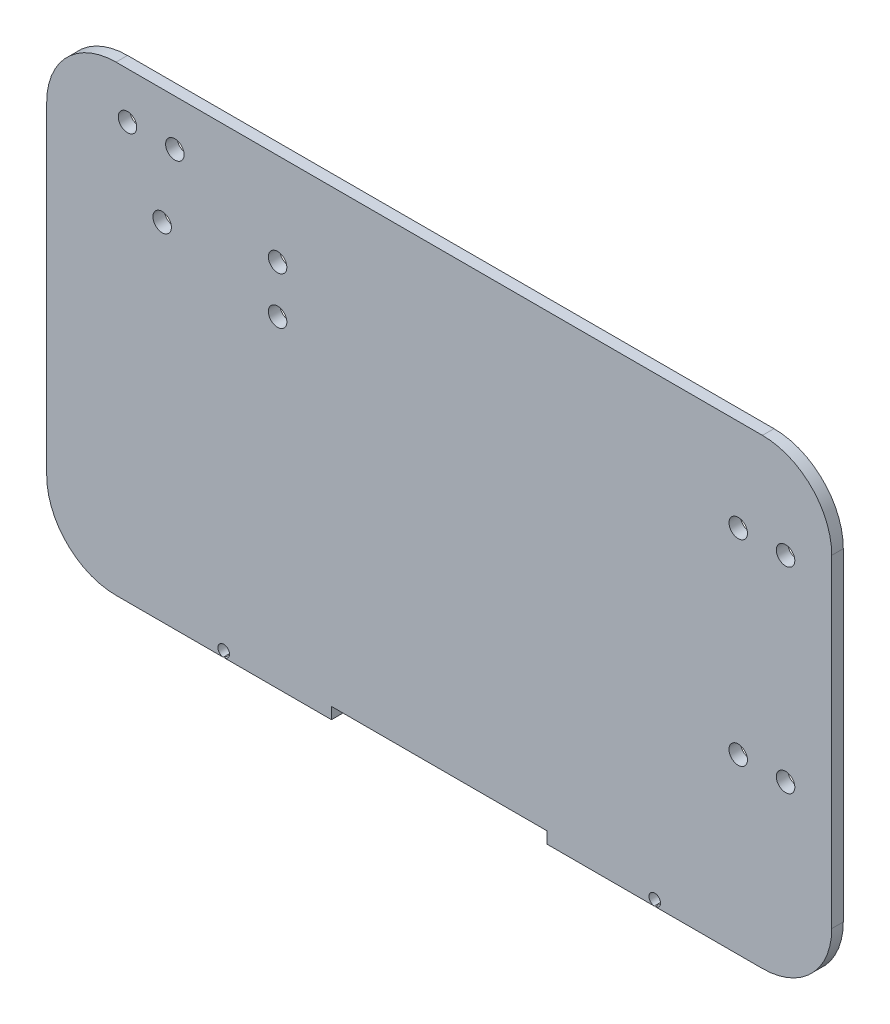
SolidWorks part; units mm, degrees
ref_plane "Alzado" through (0, 0, 0) normal (0, 0, 1) x (1, 0, 0)
ref_plane "Planta" through (0, 0, 0) normal (0, 1, 0) x (1, 0, 0)
ref_plane "Vista lateral" through (0, 0, 0) normal (1, 0, 0) x (0, 0, -1)
sketch "Croquis1" plane through (0, 0, 0) normal (0, 0, 1) x (1, 0, 0)
  line L0 (-125.4724, -88.3321) -> (154.5276, -88.3321)
  line L1 (184.5276, -58.3321) -> (184.5276, 81.6679)
  line L2 (154.5276, 111.6679) -> (-125.4724, 111.6679)
  line L3 (-155.4724, 81.6679) -> (-155.4724, -58.3321)
  arc A0 (-155.4724, -58.3321) -> (-125.4724, -88.3321) centre (-125.4724, -58.3321) ccw
  arc A1 (154.5276, -88.3321) -> (184.5276, -58.3321) centre (154.5276, -58.3321) ccw
  arc A2 (184.5276, 81.6679) -> (154.5276, 111.6679) centre (154.5276, 81.6679) ccw
  arc A3 (-125.4724, 111.6679) -> (-155.4724, 81.6679) centre (-125.4724, 81.6679) ccw
  circle A4 centre (-105.4724, 61.6679) radius 4
  circle A5 centre (-55.4724, 71.6679) radius 4
  circle A6 centre (-55.4724, 51.1679) radius 4
  circle A7 centre (144.0276, -13.3321) radius 4
  circle A8 centre (164.5276, -13.3321) radius 4
  circle A9 centre (144.0276, 71.6679) radius 4
  circle A10 centre (164.5276, 71.6679) radius 4
  circle A11 centre (-99.9724, 91.6679) radius 4
  circle A12 centre (-120.4724, 91.6679) radius 4
  dimension "D1" = 8
  dimension "D2" = 30
  dimension "D3" = 144.0276
  dimension "D4" = 164.5276
  dimension "D5" = 184.5276
  dimension "D6" = 55.4724
  dimension "D7" = 99.9724
  dimension "D8" = 105.4724
  dimension "D9" = 120.4724
  dimension "D10" = 155.4724
  dimension "D11" = 51.1679
  dimension "D12" = 61.6679
  dimension "D13" = 71.6679
  dimension "D14" = 91.6679
  dimension "D15" = 111.6679
  dimension "D16" = 13.3321
  dimension "D17" = 88.3321
extrude "Saliente-Extruir1" add sketch "Croquis1" along normal blind 5
sketch "Croquis3" plane through (0, 0, 5) normal (0, 0, 1) x (1, 0, 0)
  line L0 (-32.1391, -83.3321) -> (-32.1391, -88.3321)
  line L1 (-125.4724, -88.3321) -> (154.5276, -88.3321)
  line L2 (-125.4724, -88.3321) -> (-125.4724, -83.3321)
  line L3 (-125.4724, -83.3321) -> (154.5276, -83.3321)
  line L4 (154.5276, -88.3321) -> (154.5276, -83.3321)
  line L5 (61.1942, -83.3321) -> (61.1942, -88.3321)
  line M10 (-125.4724, -88.3321) -> (154.5276, -88.3321)
  dimension "D1" = 5
  dimension "D2" = 93.3333
  dimension "D3" = 93.3333
extrude "Cortar-Extruir1" cut sketch "Croquis3" against normal blind 10 contours L5 L3 L0 M10 region at (14.5276, -85.8321, 5)
sketch "Croquis6" plane through (0, 0, 5) normal (0, 0, 1) x (1, 0, 0)
  line L0 (-78.8058, -88.3321) -> (-78.8058, -85.8421) construction
  line L1 (-125.4724, -88.3321) -> (-32.1391, -88.3321) construction
  line L2 (14.5276, -83.3321) -> (14.5276, -88.3321) construction
  line L3 (-32.1391, -83.3321) -> (61.1942, -83.3321) construction
  circle A0 centre (-78.8058, -85.8421) radius 2.5
  circle A1 centre (107.8609, -85.8421) radius 2.5
  dimension "D2" = 5
  dimension "D1" = 2.49
extrude "Cortar-Extruir2" cut sketch "Croquis6" against normal blind 10
sketch "Croquis7" plane through (0, 0, 5) normal (0, 0, 1) x (1, 0, 0)
  line L10 (108.0843, -88.3321) -> (154.5276, -88.3321)
  line L11 (184.5276, -58.3321) -> (184.5276, 81.6679)
  line L12 (154.5276, 111.6679) -> (-125.4724, 111.6679)
  line L13 (-155.4724, 81.6679) -> (-155.4724, -58.3321)
  line L14 (-125.4724, -88.3321) -> (-79.0291, -88.3321)
  line L15 (-78.5824, -88.3321) -> (-32.1391, -88.3321)
  line L16 (-32.1391, -88.3321) -> (-32.1391, -83.3321)
  line L17 (-32.1391, -83.3321) -> (61.1942, -83.3321)
  line L18 (61.1942, -83.3321) -> (61.1942, -88.3321)
  line L19 (61.1942, -88.3321) -> (107.6375, -88.3321)
  line L20 (108.0843, -88.3321) -> (154.5276, -88.3321)
  line L21 (184.5276, -58.3321) -> (184.5276, 81.6679)
  line L22 (154.5276, 111.6679) -> (-125.4724, 111.6679)
  line L23 (-155.4724, 81.6679) -> (-155.4724, -58.3321)
  line L24 (-125.4724, -88.3321) -> (-79.0291, -88.3321)
  line L25 (-78.5824, -88.3321) -> (-32.1391, -88.3321)
  line L26 (-32.1391, -88.3321) -> (-32.1391, -83.3321)
  line L27 (-32.1391, -83.3321) -> (61.1942, -83.3321)
  line L28 (61.1942, -83.3321) -> (61.1942, -88.3321)
  line L29 (61.1942, -88.3321) -> (107.6375, -88.3321)
  circle A0 centre (164.5276, 71.6679) radius 4 construction
  circle A1 centre (144.0276, 71.6679) radius 4 construction
  circle A2 centre (164.5276, -13.3321) radius 4 construction
  circle A3 centre (144.0276, -13.3321) radius 4 construction
  circle A4 centre (-55.4724, 51.1679) radius 4 construction
  circle A5 centre (-55.4724, 71.6679) radius 4 construction
  arc A6 (108.0843, -88.3321) -> (107.6375, -88.3321) centre (107.8609, -85.8421) ccw
  arc A7 (154.5276, -88.3321) -> (184.5276, -58.3321) centre (154.5276, -58.3321) ccw
  arc A8 (184.5276, 81.6679) -> (154.5276, 111.6679) centre (154.5276, 81.6679) ccw
  arc A9 (-125.4724, 111.6679) -> (-155.4724, 81.6679) centre (-125.4724, 81.6679) ccw
  arc A10 (-155.4724, -58.3321) -> (-125.4724, -88.3321) centre (-125.4724, -58.3321) ccw
  arc A11 (-78.5824, -88.3321) -> (-79.0291, -88.3321) centre (-78.8058, -85.8421) ccw
  arc A12 (108.0843, -88.3321) -> (107.6375, -88.3321) centre (107.8609, -85.8421) ccw
  arc A13 (154.5276, -88.3321) -> (184.5276, -58.3321) centre (154.5276, -58.3321) ccw
  arc A14 (184.5276, 81.6679) -> (154.5276, 111.6679) centre (154.5276, 81.6679) ccw
  arc A15 (-125.4724, 111.6679) -> (-155.4724, 81.6679) centre (-125.4724, 81.6679) ccw
  arc A16 (-155.4724, -58.3321) -> (-125.4724, -88.3321) centre (-125.4724, -58.3321) ccw
  arc A17 (-78.5824, -88.3321) -> (-79.0291, -88.3321) centre (-78.8058, -85.8421) ccw
  circle A18 centre (-105.4724, 61.6679) radius 4 construction
  circle A19 centre (-99.9724, 91.6679) radius 4 construction
  circle A20 centre (-120.4724, 91.6679) radius 4 construction
  circle A21 centre (164.5276, 71.6679) radius 4
  circle A22 centre (144.0276, 71.6679) radius 4
  circle A23 centre (164.5276, -13.3321) radius 4
  circle A24 centre (144.0276, -13.3321) radius 4
  circle A25 centre (-55.4724, 51.1679) radius 4
  circle A26 centre (-55.4724, 71.6679) radius 4
  circle A27 centre (-105.4724, 61.6679) radius 4
  circle A28 centre (-99.9724, 91.6679) radius 4
  circle A29 centre (-120.4724, 91.6679) radius 4
  dimension "D1" = 0
